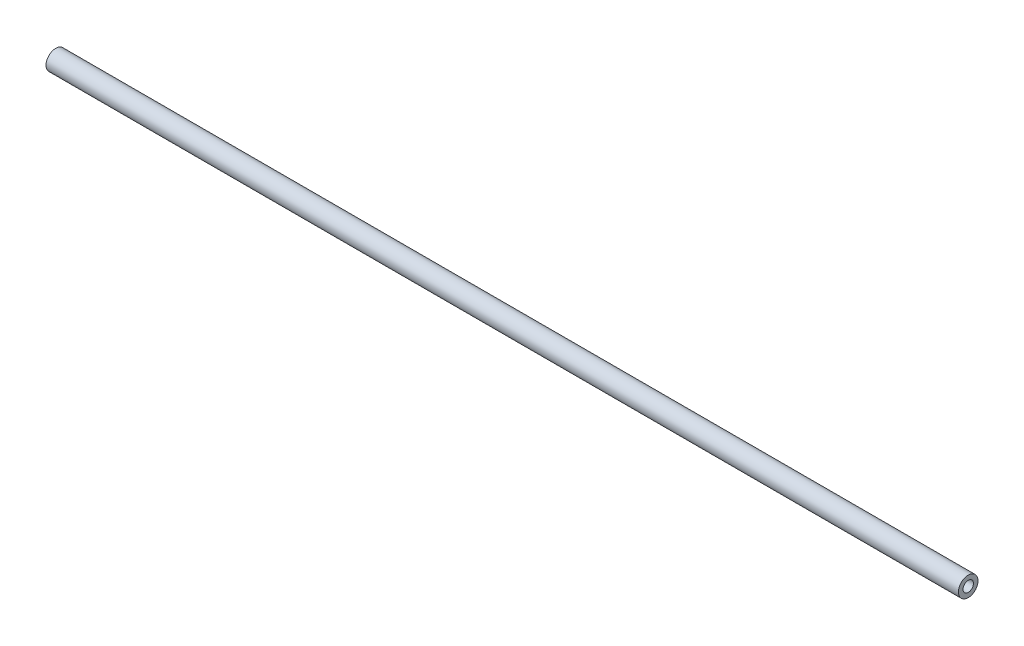
SolidWorks part; units mm, degrees
material "6061-T6 (SS)"
ref_plane "Front" through (0, 0, 0) normal (0, 0, 1) x (1, 0, 0)
ref_plane "Top" through (0, 0, 0) normal (0, 1, 0) x (1, 0, 0)
ref_plane "Right" through (0, 0, 0) normal (1, 0, 0) x (0, 0, -1)
sketch "Sketch1" plane through (0, 0, 0) normal (1, 0, 0) x (0, 0, -1)
  circle A0 centre (0, 0) radius 4.7625
  dimension "D1" = 9.525
extrude "Boss-Extrude1" add sketch "Sketch1" along normal up to surface (444.5 mm away)
hole_wizard "1/4-20 Tapped Hole1" positions "Sketch2" profile "Sketch3" tap size "1/4-20" standard "ANSI Inch"
sketch "Sketch2" plane through (0, 0, 0) normal (-1, 0, 0) x (0, 0, 1)
  point P0 (0, 0)
sketch "Sketch3" plane through (0, 0, 0) normal (0, 1, 0) x (0, 0, 1)
  line L0 (0, 0) -> (0, 18.0438)
  line L1 (0, 18.0438) -> (2.5527, 16.51)
  line L2 (2.5527, 16.51) -> (2.5527, 0)
  line L5 (2.5527, 0) -> (0, 0)
  line L10 (0, 18.0438) -> (-2.5527, 16.51) construction
  line L11 (0, -6.35) -> (0, 107.95) construction
  dimension "Tap Drill Dia." = 5.1054
  dimension "Tap Drill Depth" = 16.51
  dimension "Drill Angle" = 118
cosmetic thread "Hole Thread1"
hole_wizard "1/4-20 Tapped Hole2" positions "Sketch4" profile "Sketch5" tap size "1/4-20" standard "ANSI Inch"
sketch "Sketch4" plane through (444.5, 0, 0) normal (1, 0, 0) x (0, 0, -1)
  point P0 (0, 0)
sketch "Sketch5" plane through (444.5, 0, 0) normal (0, 1, 0) x (0, 0, -1)
  line L0 (0, 0) -> (0, 18.0438)
  line L1 (0, 18.0438) -> (2.5527, 16.51)
  line L2 (2.5527, 16.51) -> (2.5527, 0)
  line L5 (2.5527, 0) -> (0, 0)
  line L10 (0, 18.0438) -> (-2.5527, 16.51) construction
  line L11 (0, -6.35) -> (0, 107.95) construction
  dimension "Tap Drill Dia." = 5.1054
  dimension "Tap Drill Depth" = 16.51
  dimension "Drill Angle" = 118
cosmetic thread "Hole Thread2" parameters "D1"=12.7, "D2"=6.35
